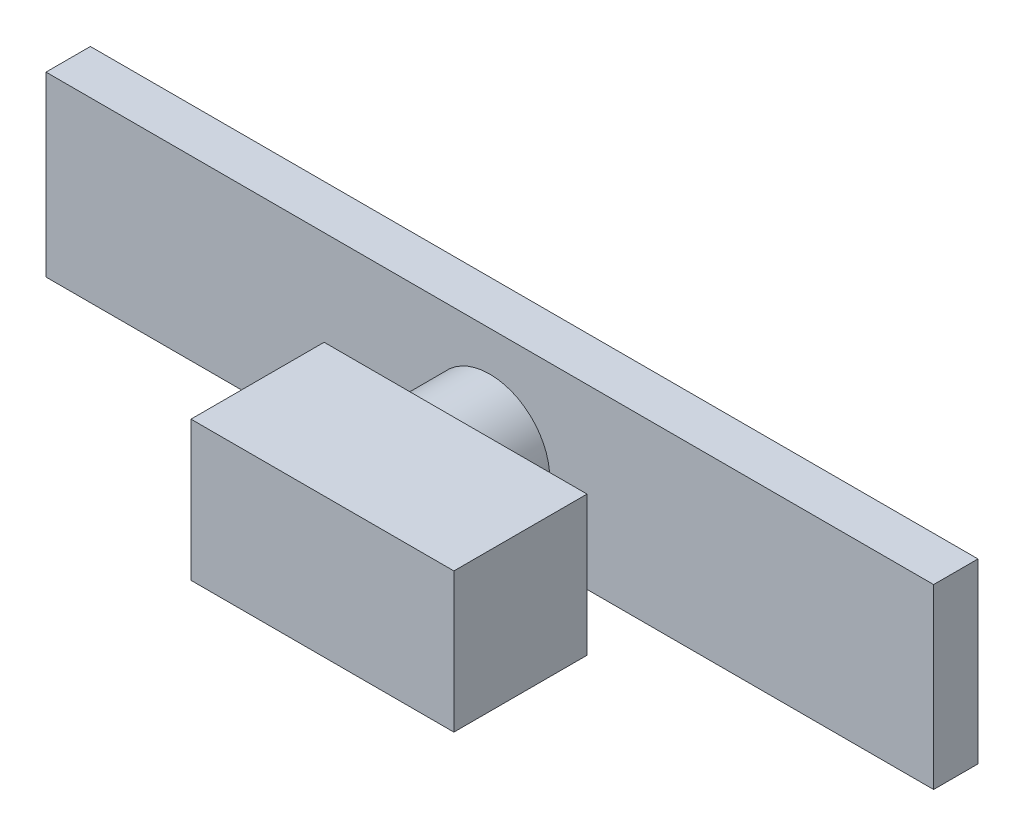
SolidWorks part; units mm, degrees
ref_plane "Front Plane" through (0, 0, 0) normal (0, 0, 1) x (1, 0, 0)
ref_plane "Top Plane" through (0, 0, 0) normal (0, 1, 0) x (1, 0, 0)
ref_plane "Right Plane" through (0, 0, 0) normal (1, 0, 0) x (0, 0, -1)
sketch "Sketch2" plane through (0, 0, 0) normal (0, 0, 1) x (1, 0, 0)
  line L1 (-47.8692, 21.2481) -> (206.1308, 21.2481)
  line L2 (-47.8692, 21.2481) -> (-47.8692, 8.5481)
  line L3 (-47.8692, 8.5481) -> (206.1308, 8.5481)
  line L4 (206.1308, 21.2481) -> (206.1308, 8.5481)
  dimension "D1" = 12.7
  dimension "D2" = 254
extrude "Boss-Extrude1" add sketch "Sketch2" along normal blind 50.8
sketch "Sketch3" plane through (0, 21.2481, 0) normal (0, 1, 0) x (1, 0, 0)
  circle A0 centre (79.1308, -28.4831) radius 17.1408
extrude "Boss-Extrude2" add sketch "Sketch3" along normal blind 19.05
sketch "Sketch4" plane through (0, 40.2981, 0) normal (0, 1, 0) x (1, 0, 0)
  line L1 (50.7675, -8.111) -> (126.0034, -8.111)
  line L2 (50.7675, -8.111) -> (50.7675, -48.0661)
  line L3 (50.7675, -48.0661) -> (126.0034, -48.0661)
  line L4 (126.0034, -8.111) -> (126.0034, -48.0661)
extrude "Boss-Extrude3" add sketch "Sketch4" along normal blind 38.1
scale "Scale2" scale about centroid uniform scaling yes scale factor 0.06
move or copy body "Body-Move/Copy1" bodies to move or copy 105 copy no rotation origin (0, 33.6669, 26.5501) rotation axis (1, 0, 0) rotation angle 90
move or copy body "Body-Move/Copy3" bodies to move or copy 106 copy no translate (-50.8, 0, -50.8)
scale "Scale5" scale about centroid uniform scaling yes scale factor 0.25
move or copy body "Body-Move/Copy4" bodies to move or copy 111 copy no translate (-50.8, 0, 50.8)
